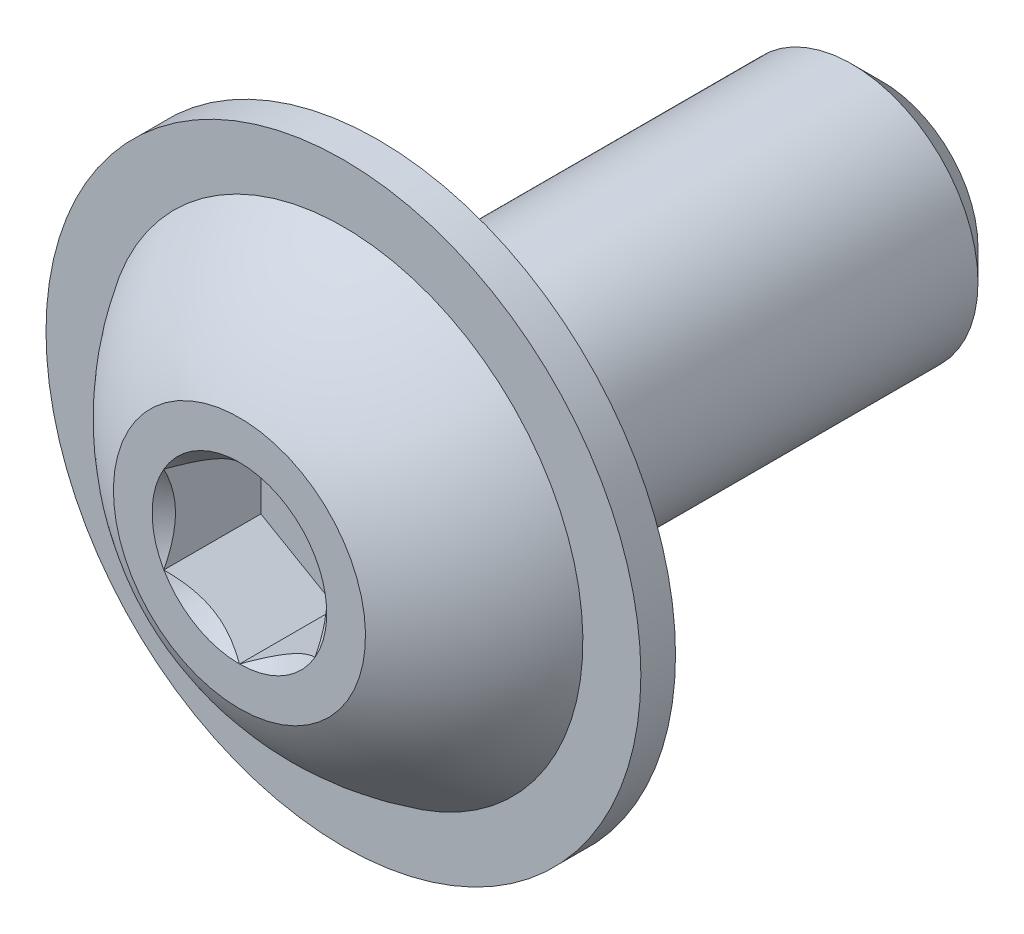
SolidWorks part; units mm, degrees
ref_plane "Front" through (0, 0, 0) normal (0, 0, 1) x (1, 0, 0)
ref_plane "Top" through (0, 0, 0) normal (0, 1, 0) x (1, 0, 0)
ref_plane "Right" through (0, 0, 0) normal (1, 0, 0) x (0, 0, -1)
sketch "Sketch1" plane through (0, 0, 0) normal (1, 0, 0) x (0, 0, -1)
  line L2 (-3.625, 2.5) -> (6.375, 2.5)
  line L3 (6.375, 2.5) -> (6.375, 0)
  line L4 (6.375, -2.5) -> (5.575, -2.5) construction
  line L6 (-4.3125, 4.75) -> (-3.625, 4.75) construction
  line L7 (6.375, 2.5) -> (6.375, -2.5) construction
  line L8 (-6.375, 0) -> (6.375, 0) construction
  line L9 (-3.625, 4.75) -> (-3.625, -4.75) construction
  line L11 (-3.625, 2.5) -> (-3.625, 0)
  line L13 (-6.375, 1.5) -> (-6.375, -1.5) construction
  line L14 (-6.375, 1.5) -> (-6.375, 2.5) construction
  line L15 (-4.3125, 4.75) -> (-4.3125, 5.9) construction
  line L16 (-4.3125, 5.9) -> (-3.625, 5.9) construction
  line L17 (-3.625, 5.9) -> (-3.625, 4.75) construction
  line L18 (-3.625, 5.9) -> (-3.625, -5.9) construction
  arc A3 (-6.375, 2.5) -> (-4.3125, 4.75) centre (-1.3892, 0) cw construction
  point P16 (3.575, -2.5)
  point P24 (0, 0)
  dimension "Thread OD" = 5
  dimension "D1" = 0.6875
  dimension "Head Height" = 2.75
  dimension "Head Diameter" = 9.5
  dimension "Length" = 10
  dimension "Drive Size" = 3
  dimension "Flange Diameter" = 11.8
  dimension "D2" = 2.8
  dimension "Thread Pitch" = 0.8
sketch "Sketch13" plane through (0, 0, 0) normal (1, 0, 0) x (0, 0, -1)
  line L1 (-3.625, 2.5) -> (6.375, 2.5)
  line L2 (-3.625, 2.5) -> (-3.625, 0)
  line L3 (-3.625, 0) -> (6.375, 0)
  line L4 (6.375, 2.5) -> (6.375, 0)
revolve "Revolve1" add sketch "Sketch13" angle 360 about L8
chamfer "Chamfer1" distance 0.6 angle 45 1 edges at (2.5, 0, -6.375)
sketch "Sketch7" plane through (0, 0, 0) normal (1, 0, 0) x (0, 0, -1)
  line L0 (-3.625, 4.75) -> (-3.625, -4.75) construction
  line L1 (-3.625, 4.75) -> (-3.625, 0)
  line L2 (-4.3125, 4.75) -> (-4.3125, 5.9)
  line L3 (-4.3125, 5.9) -> (-3.625, 5.9)
  line L4 (-3.625, 5.9) -> (-3.625, 4.75)
  line L6 (-4.3125, 4.75) -> (-3.625, 4.75) construction
  line L8 (-6.375, 0) -> (6.375, 0) construction
  line L12 (-4.3125, 4.75) -> (-3.625, 4.75) construction
  line L13 (-6.375, 0) -> (-3.625, 0)
  line L14 (-6.375, 1.5) -> (-6.375, -1.5) construction
  line L16 (-6.375, 2.5) -> (-6.375, 0)
  arc A2 (-4.3125, 4.75) -> (-6.375, 2.5) centre (-1.3892, 0) ccw construction
  arc A3 (-4.3125, 4.75) -> (-6.375, 2.5) centre (-1.3892, 0) ccw
revolve "Revolve2" add sketch "Sketch7" angle 360 mid plane about L13
sketch "Sketch5" plane through (0, 0, 6.375) normal (0, 0, 1) x (1, 0, 0)
  line L1 (1.5, -0.866) -> (1.5, 0.866)
  line L2 (1.5, 0.866) -> (0, 1.7321)
  line L3 (0, 1.7321) -> (-1.5, 0.866)
  line L4 (-1.5, 0.866) -> (-1.5, -0.866)
  line L5 (-1.5, -0.866) -> (0, -1.7321)
  line L6 (0, -1.7321) -> (1.5, -0.866)
  circle A0 centre (0, 0) radius 1.5 construction
extrude "Cut-Extrude2" cut sketch "Sketch5" against normal blind 1.925
sketch "Sketch6" plane through (0, 0, 6.375) normal (0, 0, 1) x (1, 0, 0)
  circle A0 centre (0, 0) radius 1.7321
extrude "Cut-Extrude3" cut sketch "Sketch6" against normal blind 1.925 draft 45
split "Split1" [suppressed] bodies to split 113
sketch "Sketch14" [suppressed] plane through (0, 0, -6.375) normal (0, 0, -1) x (-1, 0, 0)
  circle A0 centre (0, 0) radius 2.5 construction
  circle A1 centre (0, 0) radius 2.5
curve "Helix/Spiral1" [suppressed] pitch 0.8 height 10.8 turns 13.5
sketch "Sketch16" [suppressed] plane through (0, 0, 0) normal (1, 0, 0) x (0, 0, -1)
  line L0 (7.125, 2.5866) -> (6.325, 2.5866) construction
  line L1 (6.325, 2.5866) -> (6.725, 1.8938) construction
  line L2 (6.725, 1.8938) -> (7.125, 2.5866) construction
  line L3 (7.075, 2.5) -> (6.375, 2.5) construction
  line L4 (6.725, 2.5866) -> (6.725, 2.5) construction
  line L5 (7.1, 2.5433) -> (6.35, 2.5433) construction
  line L6 (6.775, 1.9804) -> (6.675, 1.9804) construction
  line L7 (6.725, 1.9804) -> (6.725, 1.8938) construction
  line L8 (6.675, 1.9804) -> (6.35, 2.5433)
  line L9 (6.35, 2.5433) -> (7.1, 2.5433)
  line L10 (7.1, 2.5433) -> (6.775, 1.9804)
  line L11 (6.775, 1.9804) -> (6.675, 1.9804)
  point P11 (6.725, 2.5433)
  dimension "D1" = 0.8
sweep "Cut-Sweep1" [suppressed] cut profiles "Sketch16" path "Helix/Spiral1"
sketch "Sketch17" [suppressed] plane through (0, 0, 3.625) normal (0, 0, -1) x (-1, 0, 0)
  circle A1 centre (0, 0) radius 2.5
  circle A2 centre (0, 0) radius 2.5
  dimension "D1" = 0
extrude "Boss-Extrude1" [suppressed] add sketch "Sketch17" along normal up to next draft 20
equation "\"D3@Helix/Spiral1\" = \"Length@Sketch1\" + \"D4@Helix/Spiral1\""
equation "\"D1@Chamfer1\" = \"D4@Helix/Spiral1\" * .75"
equation "\"D1@Cut-Extrude2\" = \"Head Height@Sketch1\" * .7"
equation "\"D1@Sketch1\" = \"Head Height@Sketch1\" * .25"
equation "\"D1@Cut-Extrude3\" = \"D1@Cut-Extrude2\""
equation "\"D2@Sketch1\"=\"D4@Helix/Spiral1\"*3.5"
equation "\"D4@Helix/Spiral1\"=\"Thread Pitch@Sketch1\""
equation "\"D1@Sketch16\"=\"Thread Pitch@Sketch1\""
equation "\"D2@Sketch16\"=\"D1@Sketch16\"/8"
